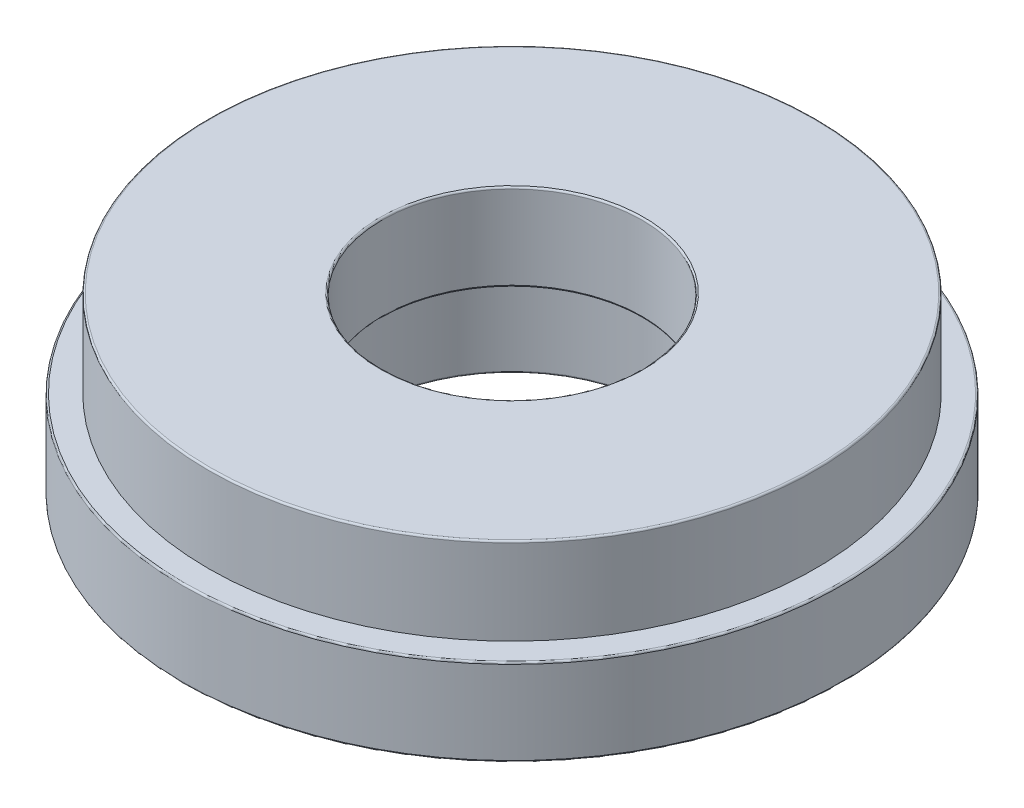
SolidWorks part; units mm, degrees
ref_plane "前视基准面" through (0, 0, 0) normal (0, 0, 1) x (1, 0, 0)
ref_plane "上视基准面" through (0, 0, 0) normal (0, 1, 0) x (1, 0, 0)
ref_plane "右视基准面" through (0, 0, 0) normal (1, 0, 0) x (0, 0, -1)
other "Configuration Table"
sketch "草图1" plane through (0, 0, 0) normal (0, 1, 0) x (1, 0, 0)
  circle A0 centre (0, 0) radius 19
  circle A1 centre (0, 0) radius 15 construction
  circle A2 centre (0, 15) radius 3.1
  circle A3 centre (12.9904, 7.5) radius 3.1
  circle A4 centre (12.9904, -7.5) radius 3.1
  circle A5 centre (0, -15) radius 3.1
  circle A6 centre (-12.9904, -7.5) radius 3.1
  circle A7 centre (-12.9904, 7.5) radius 3.1
  point P18 (0, 0)
  dimension "D1" = 6.2
  dimension "D2" = 38
  dimension "D3" = 30
  dimension "D4" = 6
extrude "凸台-拉伸1" add sketch "草图1" along normal blind 5 contours A0
extrude "切除-拉伸1" cut sketch "草图1<3>" along normal blind 4 contours A7 | A6 | A5 | A4 | A3 | A2 region at (0, 0, -15) region at (12.9904, 0, -7.5) region at (12.9904, 0, 7.5) region at (0, 0, 15) region at (-12.9904, 0, 7.5) region at (-12.9904, 0, -7.5)
sketch "草图1<3>" plane through (0, 0, 0) normal (0, 1, 0) x (1, 0, 0) same geometry as "草图1"
sketch "草图5" plane through (0, 5, 0) normal (0, 1, 0) x (1, 0, 0)
  circle A0 centre (0, 0) radius 7.5
  circle A1 centre (0, 0) radius 17.5
  dimension "D1" = 35
  dimension "D2" = 15
extrude "凸台-拉伸3" add sketch "草图5" along normal blind 5
sketch "草图8" plane through (0, 0, 0) normal (0, -1, 0) x (1, 0, 0)
  circle A0 centre (0, 0) radius 8.5
  dimension "D1" = 17
extrude "切除-拉伸4" cut sketch "草图8" against normal offset from surface (5 mm away) 5 up to face at (0, 10, 17.5)
fillet "圆角1" radius 0.1 12 edges at (0, 5, 7.5) (-12.9904, 0, -4.4) (-12.9904, 0, 10.6) (0, 0, 18.1) (12.9904, 0, 10.6) (12.9904, 0, -4.4) (0, 0, -11.9) (0, 0, -8.5) (0, 10, 7.5) (0, 10, 17.5) (0, 0, 19) (0, 5, 19)
